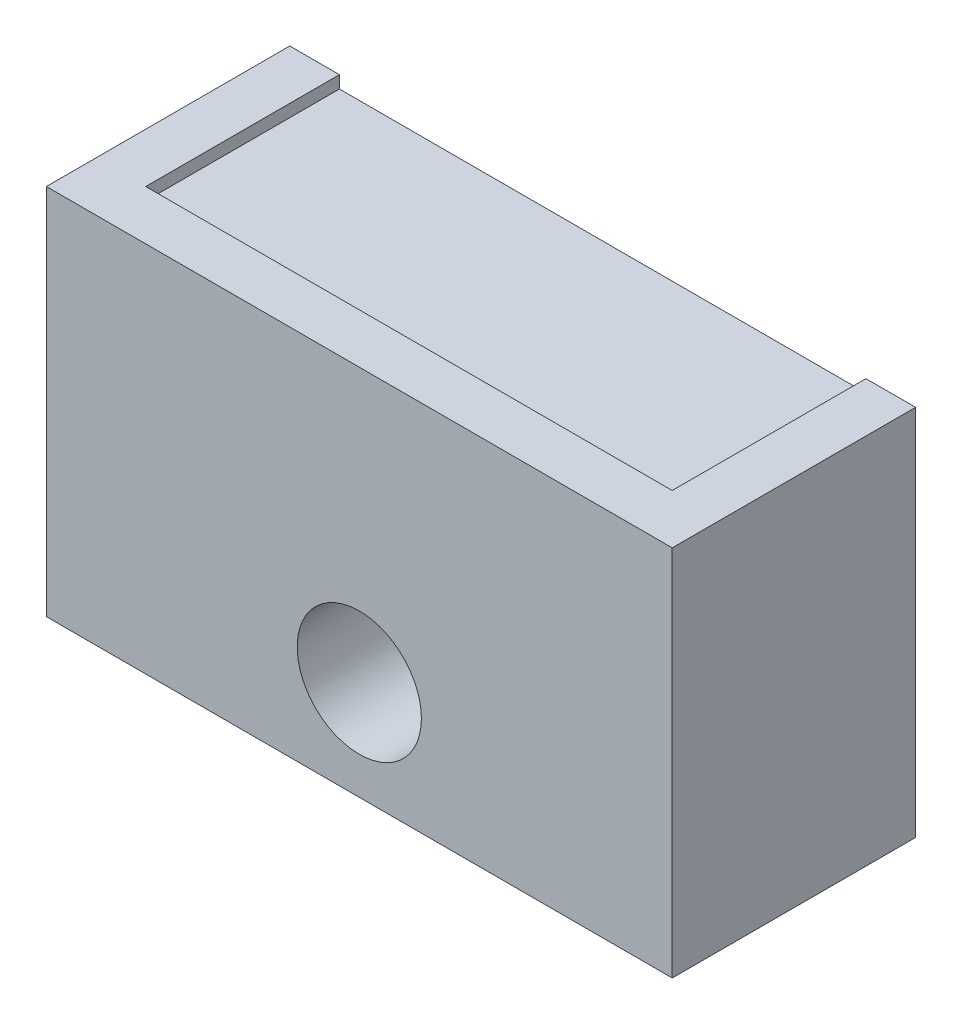
SolidWorks part; units mm, degrees
ref_plane "Plan de face" through (0, 0, 0) normal (0, 0, 1) x (1, 0, 0)
ref_plane "Plan de dessus" through (0, 0, 0) normal (0, 1, 0) x (1, 0, 0)
ref_plane "Plan de droite" through (0, 0, 0) normal (1, 0, 0) x (0, 0, -1)
sketch "Sketch2" plane through (0, 0, 0) normal (0, 0, 1) x (1, 0, 0)
  line L1 (0, 0) -> (-25.2, 0)
  line L2 (0, 0) -> (0, 15)
  line L3 (0, 15) -> (-25.2, 15)
  line L4 (-25.2, 0) -> (-25.2, 15)
  dimension "D1" = 25.2
  dimension "D2" = 15
extrude "Boss-Extrude2" add sketch "Sketch2" along normal blind 2
sketch "Sketch3" plane through (0, 0, 0) normal (0, 0, -1) x (-1, 0, 0)
  line L0 (25.2, 0) -> (0, 0) construction
  line L1 (0, 15) -> (2, 15)
  line L2 (0, 15) -> (0, 0)
  line L3 (0, 0) -> (2, 0)
  line L4 (2, 15) -> (2, 0)
  line L5 (0, 15) -> (25.2, 15) construction
  line L6 (25.2, 0) -> (23.2, 0)
  line L7 (25.2, 0) -> (25.2, 15)
  line L8 (25.2, 15) -> (23.2, 15)
  line L9 (23.2, 0) -> (23.2, 15)
  line L11 (2, 15) -> (23.2, 15)
  line L12 (2, 15) -> (2, 13)
  line L13 (2, 13) -> (23.2, 13)
  line L14 (23.2, 15) -> (23.2, 13)
  line M3 (0, 15) -> (0, 0)
  line M4 (0, 0) -> (25.2, 0)
  line M5 (25.2, 0) -> (25.2, 15)
  line M6 (25.2, 15) -> (0, 15)
  dimension "D1" = 2
  dimension "D2" = 2
  dimension "D3" = 2
extrude "Boss-Extrude3" add sketch "Sketch3" along normal blind 7.8 contours L4 M6 M3 M4 | L4 L13 L9 M6 | L9 M4 M5 M6 region at (-1, 7.5, 0) region at (-12.6, 14, 0) region at (-24.2, 7.5, 0)
sketch "Sketch8" plane through (0, 0, 0) normal (0, 0, -1) x (-1, 0, 0)
  line L0 (23.2, 0) -> (23.2, 13) construction
  line L1 (2, 0) -> (23.2, 0)
  line L2 (2, 0) -> (2, 8.1631)
  line L3 (2, 8.1631) -> (23.2, 8.1631)
  line L4 (23.2, 0) -> (23.2, 8.1631)
  line L5 (23.2, 8.1631) -> (2, 8.1631) construction
  line L7 (4.35, 8.1631) -> (2, 8.1631)
  line L8 (4.35, 8.1631) -> (4.35, 0)
  line L9 (4.35, 0) -> (2, 0)
  line L10 (2, 8.1631) -> (2, 0)
  line L11 (9.35, 8.1631) -> (15.8479, 8.1631)
  line L12 (9.35, 8.1631) -> (9.35, 0)
  line L13 (9.35, 0) -> (15.8479, 0)
  line L14 (15.8479, 8.1631) -> (15.8479, 0)
  line L15 (20.85, 8.1631) -> (23.2, 8.1631)
  line L16 (20.85, 8.1631) -> (20.85, 0)
  line L17 (20.85, 0) -> (23.2, 0)
  line L18 (23.2, 8.1631) -> (23.2, 0)
  line M10 (2, 13) -> (2, 0)
  line M11 (2, 0) -> (23.2, 0)
  line M12 (23.2, 0) -> (23.2, 13)
  dimension "D1" = 6.4979
  dimension "D2" = 2.35
  dimension "D3" = 2.35
  dimension "D4" = 5
  dimension "D5" = 5.0021
  dimension "D6" = 8.1631
extrude "Boss-Extrude6" add sketch "Sketch8" along normal blind 7.8 contours L8 L3 M10 M11 | L14 L3 L12 M11 | L3 L16 M11 M12 region at (-3.175, 4.0815, 0) region at (-12.5989, 4.0815, 0) region at (-22.025, 4.0815, 0)
sketch "Sketch9" plane through (0, 0, 0) normal (0, 0, -1) x (-1, 0, 0)
  line L1 (4.35, 8.1631) -> (9.35, 8.1631)
  line L2 (4.35, 8.1631) -> (4.35, 0)
  line L3 (4.35, 0) -> (9.35, 0)
  line L4 (9.35, 8.1631) -> (9.35, 0)
  line L5 (15.8479, 8.1631) -> (20.85, 8.1631)
  line L6 (15.8479, 8.1631) -> (15.8479, 0)
  line L7 (15.8479, 0) -> (20.85, 0)
  line L8 (20.85, 8.1631) -> (20.85, 0)
extrude "Boss-Extrude7" add sketch "Sketch9" along normal blind 1.3
sketch "Sketch10" plane through (0, 15, 0) normal (0, 1, 0) x (1, 0, 0)
  line L0 (0, -2) -> (-25.2, -2) construction
  line L1 (-2, 7.8) -> (-23.2, 7.8)
  line L2 (-2, 7.8) -> (-2, 0)
  line L3 (-2, 0) -> (-23.2, 0)
  line L4 (-23.2, 7.8) -> (-23.2, 0)
  line L5 (-25.2, -2) -> (-25.2, 7.8) construction
  dimension "D1" = 2
  dimension "D2" = 2
extrude "Cut-Extrude3" cut sketch "Sketch10" against normal blind 0.5
sketch "Sketch12" plane through (0, 0, 2) normal (0, 0, 1) x (1, 0, 0)
  line L1 (0, 0) -> (0, 15) construction
  line L2 (-25.2, 0) -> (0, 0) construction
  circle A0 centre (-12.6, 4) radius 1
  dimension "D1" = 2
  dimension "D2" = 12.6
  dimension "D3" = 4
extrude "Cut-Extrude4" cut sketch "Sketch12" against normal through all
sketch "Sketch13" plane through (0, 0, 2) normal (0, 0, 1) x (1, 0, 0)
  circle A0 centre (-12.6, 4) radius 2.5
  dimension "D1" = 5
extrude "Cut-Extrude5" cut sketch "Sketch13" against normal blind 5.6348
